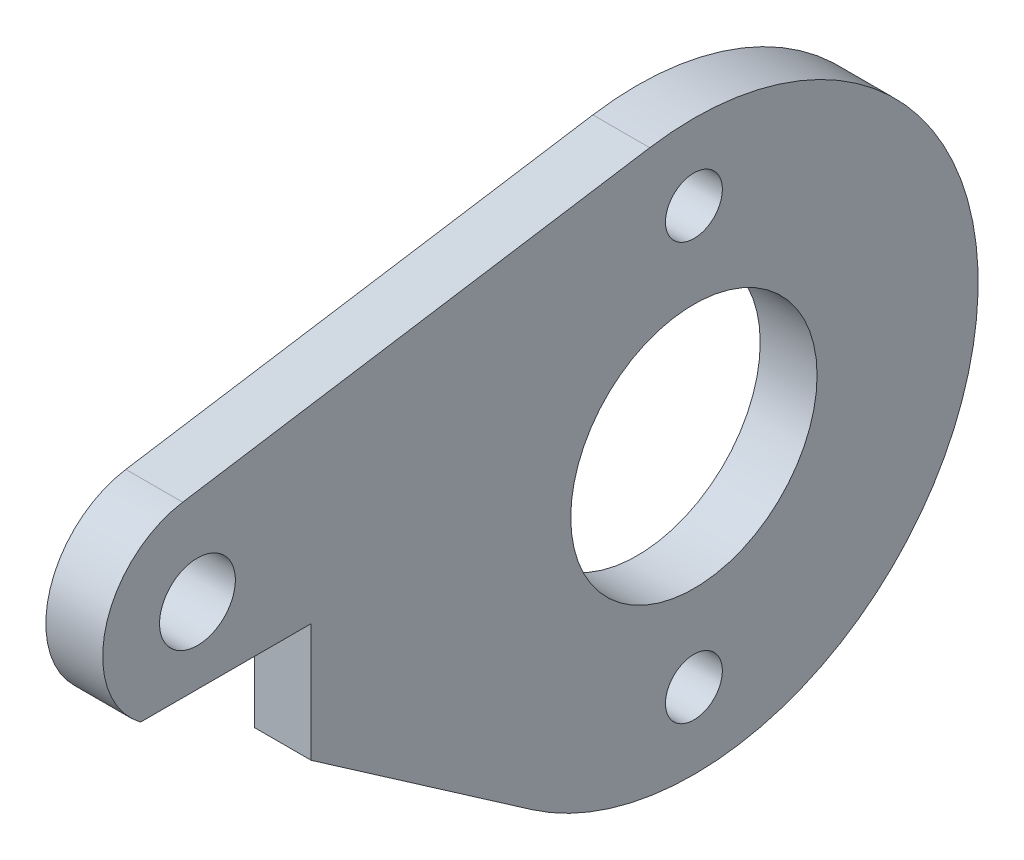
SolidWorks part; units mm, degrees
ref_plane "Plan de face" through (0, 0, 0) normal (0, 0, 1) x (1, 0, 0)
ref_plane "Plan de dessus" through (0, 0, 0) normal (0, 1, 0) x (1, 0, 0)
ref_plane "Plan de droite" through (0, 0, 0) normal (1, 0, 0) x (0, 0, -1)
sketch "Esquisse1" plane through (0, 0, 0) normal (-1, 0, 0) x (0, 0, 1)
  line L0 (29.0493, 1.8913) -> (8.548, -12.3261)
  line L1 (2.3318, 14.8176) -> (26.9773, 10.9392)
  arc A0 (8.548, -12.3261) -> (2.3318, 14.8176) centre (0, 0) cw
  arc A1 (26.9773, 10.9392) -> (29.0493, 1.8913) centre (26.2, 6) cw
  circle A2 centre (0, 0) radius 6.5 construction
  circle A3 centre (0, 0) radius 6.5
  circle A5 centre (0, 11) radius 1.5
  circle A6 centre (0, -11) radius 1.5
  circle A7 centre (0, 0) radius 15 construction
  circle A8 centre (26.2, 6) radius 2
  dimension "D1" = 3
  dimension "D2" = 4
  dimension "D3" = 5
extrude "Boss.-Extru.1" add sketch "Esquisse1" against normal blind 3
sketch "Esquisse2" plane through (3, 0, 0) normal (1, 0, 0) x (0, 0, -1)
  line L0 (-29.2061, 2) -> (-20.2, 2)
  line L1 (-8.548, -12.3261) -> (-29.0493, 1.8913) construction
  line L2 (-20.2, 2) -> (-20.2, -4.2456)
  line L3 (-20.2, -4.2456) -> (-29.2061, 2)
  line L6 (-21.2, 1) -> (-31.2, 1) construction
  line L7 (-21.2, -9) -> (-21.2, 1) construction
  dimension "D1" = 1
  dimension "D2" = 1
extrude "Enlèv. mat.-Extru.1" cut sketch "Esquisse2" against normal through all
